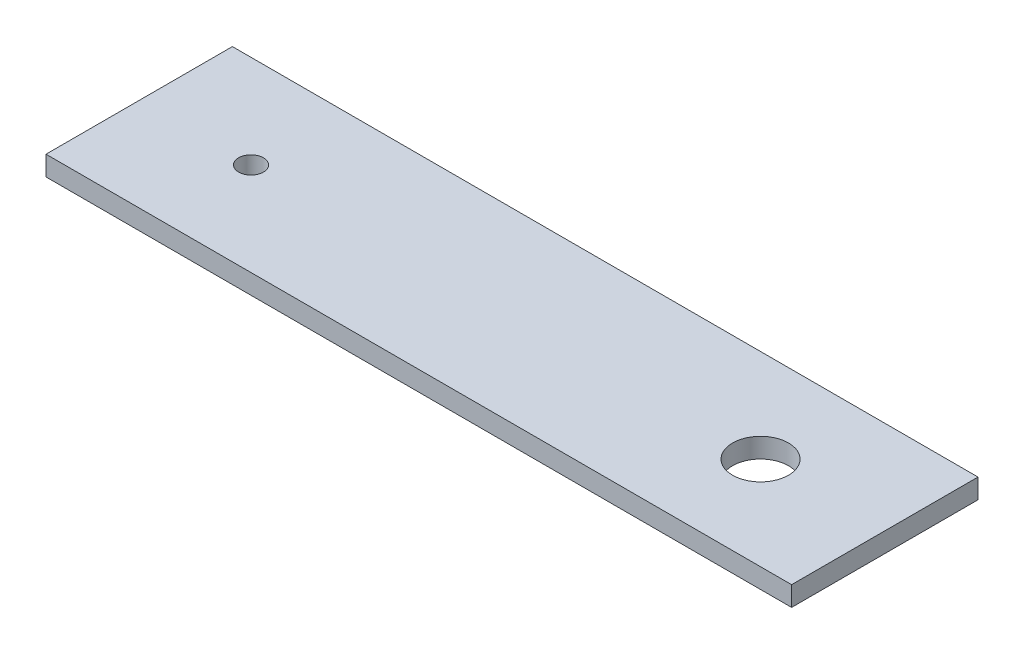
SolidWorks part; units mm, degrees
ref_plane "Front" through (0, 0, 0) normal (0, 0, 1) x (1, 0, 0)
ref_plane "Top" through (0, 0, 0) normal (0, 1, 0) x (1, 0, 0)
ref_plane "Right" through (0, 0, 0) normal (1, 0, 0) x (0, 0, -1)
sketch "Sketch1" plane through (0, 0, 0) normal (0, 1, 0) x (1, 0, 0)
  line L1 (0, 0) -> (120, 0)
  line L2 (0, 0) -> (0, 30)
  line L3 (0, 30) -> (120, 30)
  line L4 (120, 0) -> (120, 30)
  dimension "D1" = 120
  dimension "D2" = 30
extrude "Boss-Extrude1" add sketch "Sketch1" along normal blind 3.175
sketch "Sketch2" plane through (0, 3.175, 0) normal (0, 1, 0) x (1, 0, 0)
  line L0 (0, 30) -> (0, 0) construction
  line L1 (120, 30) -> (0, 30) construction
  line L2 (120, 0) -> (120, 30) construction
  circle A0 centre (18, 15) radius 2
  circle A1 centre (100, 15) radius 4.5
  dimension "D1" = 18
  dimension "D3" = 15
  dimension "D2" = 15
  dimension "D4" = 20
extrude "Cut-Extrude1" cut sketch "Sketch2" against normal blind 3.175
